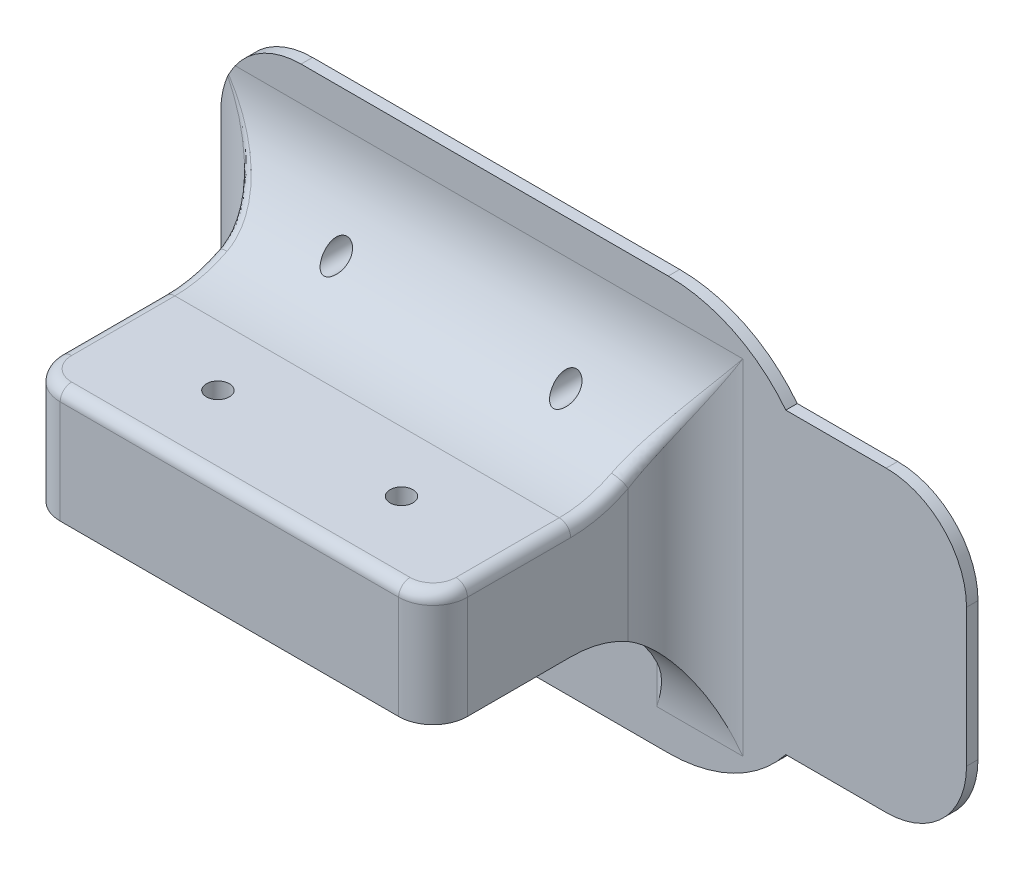
SolidWorks part; units mm, degrees
ref_plane "Front Plane" through (0, 0, 0) normal (0, 0, 1) x (1, 0, 0)
ref_plane "Top Plane" through (0, 0, 0) normal (0, 1, 0) x (1, 0, 0)
ref_plane "Right Plane" through (0, 0, 0) normal (1, 0, 0) x (0, 0, -1)
sketch "Sketch1" plane through (0, 0, 0) normal (0, 0, 1) x (1, 0, 0)
  line L0 (-18, 11) -> (-18, -11)
  line L1 (-16, -13) -> (16, -13)
  line L2 (-16, 13) -> (16, 13)
  line L3 (24.6603, 8) -> (35, 8)
  line L4 (55, 0) -> (-55, 0) construction
  line L5 (24.6603, -8) -> (35, -8)
  line L6 (37, 6) -> (37, -6)
  arc A0 (16, 13) -> (22.9282, 9) centre (16, 5) cw
  arc A1 (22.9282, 9) -> (24.6603, 8) centre (24.6603, 10) ccw
  arc A2 (22.9282, -9) -> (24.6603, -8) centre (24.6603, -10) cw
  arc A3 (16, -13) -> (22.9282, -9) centre (16, -5) ccw
  arc A4 (35, -8) -> (37, -6) centre (35, -6) ccw
  arc A5 (35, 8) -> (37, 6) centre (35, 6) cw
  arc A6 (-18, -11) -> (-16, -13) centre (-16, -11) ccw
  arc A7 (-18, 11) -> (-16, 13) centre (-16, 11) cw
  point P5 (-18, 0)
  point P7 (0, 13)
  point P21 (37, -8)
  point P24 (37, 8)
  point P27 (-18, -13)
  point P30 (-18, 13)
  point P31 (37, 0)
  dimension "D3" = 2
  dimension "D4" = 2
  dimension "D7" = 8
  dimension "D8" = 2
  dimension "D1" = 26
  dimension "D2" = 34
  dimension "D5" = 16
  dimension "D6" = 55
extrude "Insert in sheet metal hole" add sketch "Sketch1" along normal blind 1
sketch "Sketch10" plane through (0, 0, 1) normal (0, 0, 1) x (1, 0, 0)
  line L12 (26.247, -13) -> (35, -13)
  line L13 (42, -6) -> (42, 6)
  line L14 (35, 13) -> (26.247, 13)
  line L15 (16, 18) -> (-16, 18)
  line L16 (-23, 11) -> (-23, -11)
  line L17 (-16, -18) -> (16, -18)
  line L18 (26.247, -13) -> (35, -13)
  line L19 (42, -6) -> (42, 6)
  line L20 (35, 13) -> (26.247, 13)
  line L21 (16, 18) -> (-16, 18)
  line L22 (-23, 11) -> (-23, -11)
  line L23 (-16, -18) -> (16, -18)
  arc A16 (16, -18) -> (26.247, -13) centre (16, -5) ccw
  arc A17 (35, -13) -> (42, -6) centre (35, -6) ccw
  arc A18 (42, 6) -> (35, 13) centre (35, 6) ccw
  arc A19 (26.247, 13) -> (16, 18) centre (16, 5) ccw
  arc A20 (-16, 18) -> (-23, 11) centre (-16, 11) ccw
  arc A21 (-23, -11) -> (-16, -18) centre (-16, -11) ccw
  arc A22 (16, -18) -> (26.247, -13) centre (16, -5) ccw
  arc A23 (35, -13) -> (42, -6) centre (35, -6) ccw
  arc A24 (42, 6) -> (35, 13) centre (35, 6) ccw
  arc A25 (26.247, 13) -> (16, 18) centre (16, 5) ccw
  arc A26 (-16, 18) -> (-23, 11) centre (-16, 11) ccw
  arc A27 (-23, -11) -> (-16, -18) centre (-16, -11) ccw
  dimension "D1" = 5
extrude "Boss-Extrude5" add sketch "Sketch10" along normal blind 1
sketch "Sketch2" plane through (-18, 0, 0) normal (-1, 0, 0) x (0, 0, 1)
  line L0 (0, 5) -> (24, 5)
  line L2 (24, 5) -> (24, 0)
  line L3 (24, 0) -> (0, 0)
  line L4 (0, 0) -> (0, 5)
  line L5 (0, 11) -> (0, -11) construction
  line L6 (2, 11) -> (2, -11) construction
  dimension "D1" = 22
  dimension "D2" = 5
extrude "LED backing" add sketch "Sketch2" against normal up to surface (55 mm away) up to face at (37, 0, 0.5)
sketch "Sketch3" plane through (0, 0, 0) normal (0, -1, 0) x (1, 0, 0)
  line L0 (-8, 2) -> (-8, 17.25) construction
  line L2 (-8, 17.25) -> (8, 17.25) construction
  line L3 (8, 17.25) -> (8, 2) construction
  line L5 (37, 2) -> (-18, 2) construction
  circle A0 centre (-8, 17.25) radius 1
  circle A1 centre (8, 17.25) radius 1
  point P10 (0, 17.25)
  dimension "D1" = 2
  dimension "D2" = 15.25
  dimension "D3" = 16
extrude "LED screwholes" cut sketch "Sketch3" against normal blind 10
sketch "Sketch5" plane through (0, 0, 0) normal (0, -1, 0) x (1, 0, 0)
  line L1 (37, 2) -> (-18, 2) construction
  line L8 (37, 24) -> (17.5, 24)
  line L9 (37, 24) -> (37, 2)
  line L10 (37, 2) -> (17.5, 2)
  line L11 (17.5, 24) -> (17.5, 2)
  circle A2 centre (8, 17.25) radius 1 construction
  dimension "D1" = 9.5
extrude "LED backing cleanup" cut sketch "Sketch5" against normal through all both and the other way through all
fillet "Fillet1" radius 3 2 edges at (17.5, 2.5, 24) (-18, 2.5, 24)
sketch "Sketch6" plane through (0, 0, 0) normal (0, -1, 0) x (1, 0, 0)
  line L17 (14.5, 24) -> (-15, 24)
  line L18 (17.5, 2) -> (17.5, 21)
  line L19 (-18, 2) -> (17.5, 2)
  line L20 (-18, 21) -> (-18, 2)
  line L22 (14.5, 24) -> (-15, 24)
  line L23 (17.5, 2) -> (17.5, 21)
  line L24 (-18, 2) -> (-16.5, 2)
  line L25 (-18, 21) -> (-18, 2)
  line L26 (-16.5, 3.5) -> (-16.5, 2)
  line L27 (16, 3.5) -> (16, 2)
  line L28 (16, 2) -> (17.5, 2)
  line L30 (14.5, 22.5) -> (-15, 22.5)
  line L31 (16, 3.5) -> (16, 21)
  line L32 (-16.5, 3.5) -> (16, 3.5)
  line L33 (-16.5, 21) -> (-16.5, 3.5)
  line L34 (14.5, 22.5) -> (-15, 22.5)
  line L35 (16, 3.5) -> (16, 21)
  line L37 (-16.5, 21) -> (-16.5, 3.5)
  arc A8 (17.5, 21) -> (14.5, 24) centre (14.5, 21) ccw
  arc A9 (-15, 24) -> (-18, 21) centre (-15, 21) ccw
  arc A10 (17.5, 21) -> (14.5, 24) centre (14.5, 21) ccw
  arc A11 (-15, 24) -> (-18, 21) centre (-15, 21) ccw
  arc A14 (16, 21) -> (14.5, 22.5) centre (14.5, 21) ccw
  arc A15 (-15, 22.5) -> (-16.5, 21) centre (-15, 21) ccw
  arc A16 (16, 21) -> (14.5, 22.5) centre (14.5, 21) ccw
  arc A17 (-15, 22.5) -> (-16.5, 21) centre (-15, 21) ccw
  dimension "D1" = 0
  dimension "D2" = 1.5
extrude "Boss-Extrude3" add sketch "Sketch6" along normal blind 5
fillet "Fillet2" radius 10 3 edges at (-0.25, 5, 2) (16.75, -5, 2) (-17.25, -5, 2)
fillet "Fillet3" radius 5 2 edges at (17.5, 0, 2) (-18, 0, 2)
fillet "Fillet4" radius 1 8 edges at (-16.5, 0, 11.5) (-16.0607, 0, 22.0607) (16, 0, 11.5) (15.5607, 0, 22.0607) (-0.25, 0, 22.5) (-16.5, -7.5, 2) (-0.25, 0, 2) (16, -7.5, 2)
sketch "Sketch7" plane through (0, 0, 2) normal (0, 0, 1) x (1, 0, 0)
  line L3 (15, -1) -> (-15.5, -1) construction
  line L4 (15, -15) -> (15, -1) construction
  line L5 (-15.5, -1) -> (-15.5, -15) construction
  circle A0 centre (-13, -3.5) radius 2.5
  circle A1 centre (12.5, -3.5) radius 2.5
  dimension "D1" = 5
extrude "LED wire holes" cut sketch "Sketch7" against normal through all
sketch "Sketch8" plane through (0, 0, 2) normal (0, 0, 1) x (1, 0, 0)
  line L2 (16, 18) -> (-16, 18) construction
  line L3 (-16, -18) -> (16, -18) construction
  circle A0 centre (0, -8) radius 1
  circle A1 centre (-10, 8) radius 1
  circle A2 centre (10, 8) radius 1
  dimension "D1" = 2
  dimension "D2" = 20
  dimension "D3" = 10
  dimension "D4" = 10
  dimension "D5" = 10
extrude "Screwholes for backing" cut sketch "Sketch8" against normal through all both and the other way through all
sketch "Sketch9" plane through (0, 0, 2) normal (0, 0, 1) x (1, 0, 0)
  line L1 (-5, -1.75) -> (5, -1.75)
  line L2 (-5, -1.75) -> (-5, -3.75)
  line L3 (-5, -3.75) -> (5, -3.75)
  line L4 (5, -1.75) -> (5, -3.75)
  line L5 (-16, 0) -> (15, 0) construction
  line L6 (-15.5, 0) -> (15, 0) construction
  point P6 (0, -1.75)
  dimension "D1" = 2
  dimension "D2" = 1.75
  dimension "D3" = 10
extrude "Boss-Extrude4" add sketch "Sketch9" along normal blind 1
fillet "Fillet5" radius 3 3 edges at (5, -2.75, 2) (-5, -2.75, 2) (0, -3.75, 2)
fillet "Fillet6" radius 1 9 edges at (19.137, 10.0695, 3.3) (17.5, 5.3407, 9.4118) (17.5, 5, 16.5) (16.6213, 5, 23.1213) (-0.25, 5, 24) (-17.1213, 5, 23.1213) (-18, 5, 16.5) (-18, 5.3407, 9.4118) (-18.4202, 7.8647, 4.9937)
